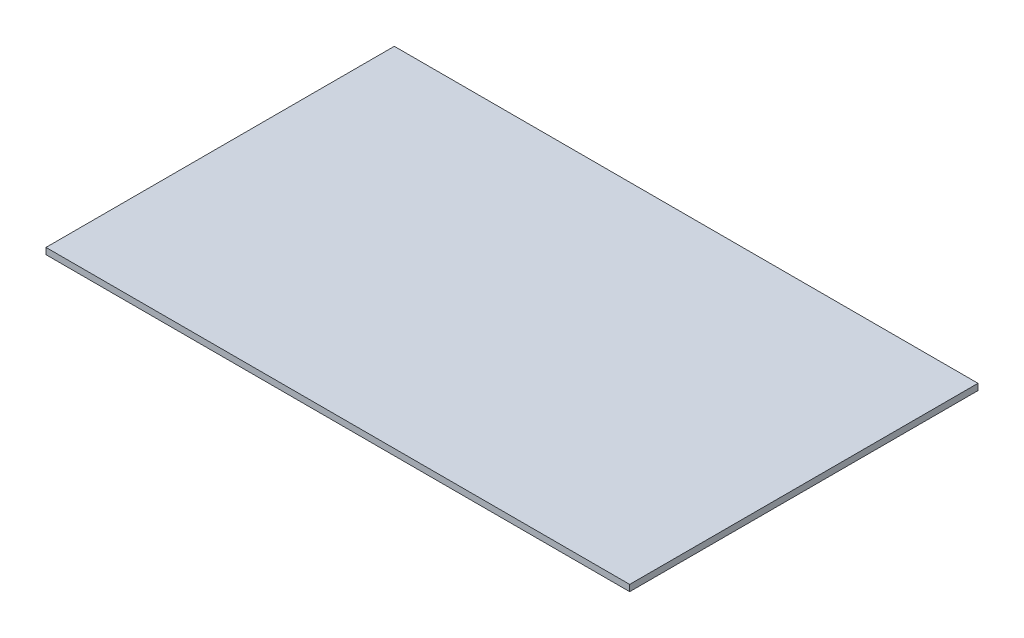
SolidWorks part; units mm, degrees
ref_plane "Спереди" through (0, 0, 0) normal (0, 0, 1) x (1, 0, 0)
ref_plane "Сверху" through (0, 0, 0) normal (0, 1, 0) x (1, 0, 0)
ref_plane "Справа" through (0, 0, 0) normal (1, 0, 0) x (0, 0, -1)
sketch "Эскиз1" plane through (0, 0, 0) normal (0, 1, 0) x (1, 0, 0)
  line L0 (-1000, 0) -> (49000, 0) construction
  line L1 (0, -1000) -> (0, 49000) construction
  line L2 (46, -1000) -> (46, 49000) construction
  line L3 (-46, -1000) -> (-46, 49000) construction
  line L4 (-1000, -27.45) -> (49000, -27.45) construction
  line L5 (-1000, 27.45) -> (49000, 27.45) construction
  line L6 (-46, 27.45) -> (-46, -27.45)
  line L7 (-46, -27.45) -> (46, -27.45)
  line L8 (46, -27.45) -> (46, 27.45)
  line L9 (46, 27.45) -> (-46, 27.45)
  dimension "D1" = 46
  dimension "D2" = 46
  dimension "D3" = 27.45
  dimension "D4" = 27.45
extrude "Бобышка-Вытянуть1" add sketch "Эскиз1" along normal blind 1
